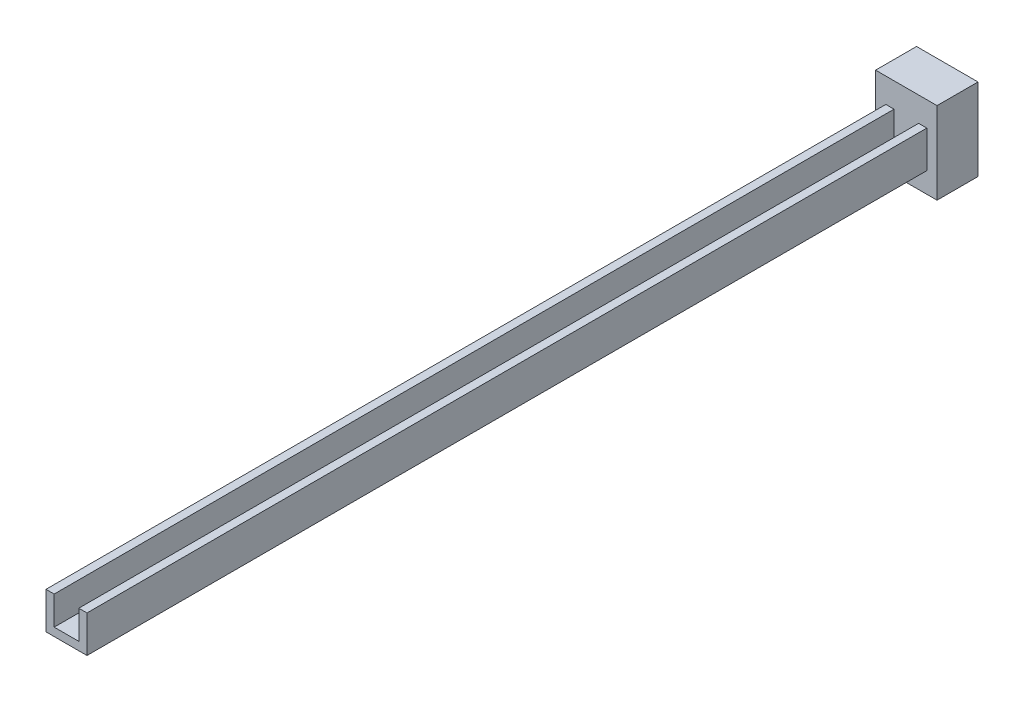
SolidWorks part; units mm, degrees
ref_plane "正面" through (0, 0, 0) normal (0, 0, 1) x (1, 0, 0)
ref_plane "平面" through (0, 0, 0) normal (0, 1, 0) x (1, 0, 0)
ref_plane "右側面" through (0, 0, 0) normal (1, 0, 0) x (0, 0, -1)
sketch "ｽｹｯﾁ1" plane through (0, 0, 0) normal (0, 0, 1) x (1, 0, 0)
  line L0 (-5, 9) -> (-5, 0)
  line L1 (-5, 0) -> (5, 0)
  line L2 (5, 0) -> (5, 9)
  line L3 (5, 9) -> (3, 9)
  line L4 (3, 9) -> (3, 2)
  line L5 (3, 2) -> (-3, 2)
  line L6 (-3, 2) -> (-3, 9)
  line L7 (-3, 9) -> (-5, 9)
  dimension "D1" = 9
  dimension "D2" = 9
  dimension "D3" = 10
  dimension "D4" = 5
  dimension "D5" = 2
  dimension "D6" = 2
  dimension "D7" = 2
extrude "ﾎﾞｽ - 押し出し1" add sketch "ｽｹｯﾁ1" along normal blind 245
sketch "ｽｹｯﾁ2" plane through (0, 0, 0) normal (0, -1, 0) x (1, 0, 0)
  line L0 (-5, 245) -> (5, 245) construction
  circle A0 centre (0, 225) radius 2.5
  circle A1 centre (0, 217) radius 2.5
  circle A2 centre (0, 122.5) radius 2.5
  circle A3 centre (0, 209) radius 2.5
  circle A4 centre (0, 193) radius 2.5
  circle A5 centre (0, 161) radius 2.5
  dimension "D1" = 20
  dimension "D3" = 5
  dimension "D4" = 5
  dimension "D5" = 5
  dimension "D6" = 122.5
  dimension "D7" = 5
  dimension "D8" = 8
  dimension "D9" = 5
  dimension "D10" = 16
  dimension "D11" = 5
  dimension "D12" = 32
  dimension "D2" = 28
extrude "ｶｯﾄ - 押し出し1" cut sketch "ｽｹｯﾁ2" against normal through all
ref_plane "平面1" through (0, 0, 122.5) normal (0, 0, 1) x (1, 0, 0)
mirror "ﾐﾗｰ1" about plane through (0, 0, 122.5) normal (0, 0, 1) of "ｶｯﾄ - 押し出し1"
sketch "ｽｹｯﾁ3" plane through (0, 0, 0) normal (0, -1, 0) x (1, 0, 0)
  line L0 (-5, 0) -> (-5, 40)
  line L1 (-5, 245) -> (-5, 0) construction
  line L2 (-5, 40) -> (5, 40)
  line L3 (5, 245) -> (5, 0) construction
  line L4 (5, 40) -> (5, 0)
  line L5 (5, 0) -> (-5, 0)
  dimension "D1" = 40
extrude "ｶｯﾄ - 押し出し2" cut sketch "ｽｹｯﾁ3" against normal through all both
sketch "ｽｹｯﾁ5" plane through (0, 0, 40) normal (0, 0, -1) x (-1, 0, 0)
  line L0 (-7.5, 15) -> (-7.5, -5)
  line L1 (-7.5, -5) -> (7.5, -5)
  line L2 (7.5, -5) -> (7.5, 15)
  line L3 (7.5, 15) -> (-7.5, 15)
  dimension "D1" = 15
  dimension "D2" = 7.5
  dimension "D3" = 20
  dimension "D4" = 15
extrude "ﾎﾞｽ - 押し出し3" add sketch "ｽｹｯﾁ5" along normal blind 10
equation "\"D2@ｽｹｯﾁ5\"=\"D1@ｽｹｯﾁ5\"/2"
